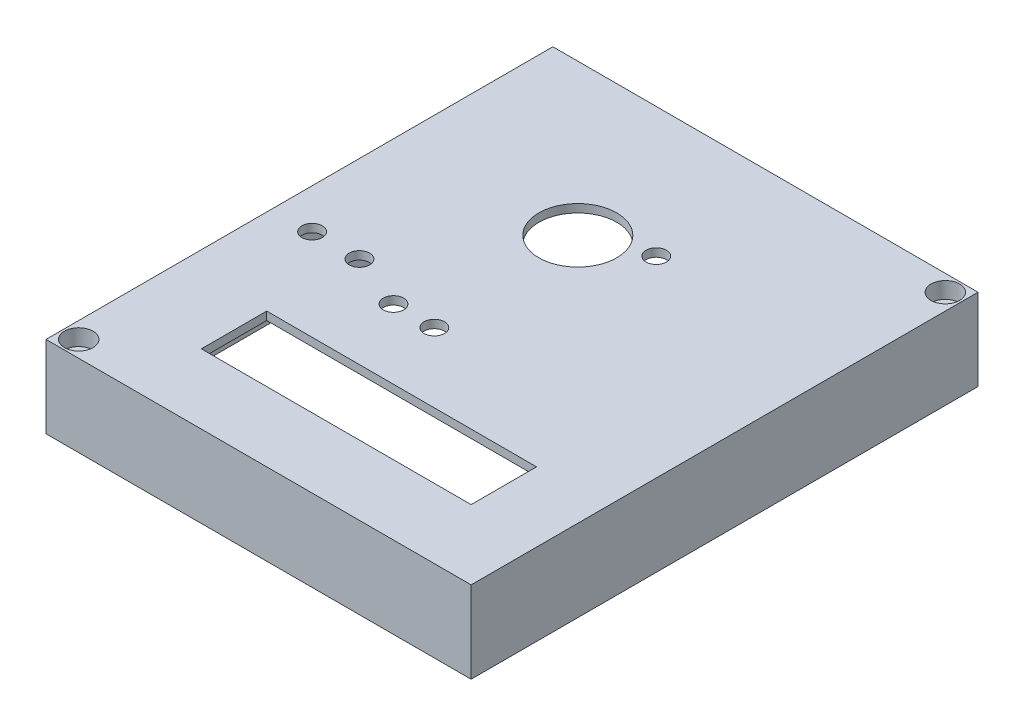
SolidWorks part; units mm, degrees
ref_plane "Front Plane" through (0, 0, 0) normal (0, 0, 1) x (1, 0, 0)
ref_plane "Top Plane" through (0, 0, 0) normal (0, 1, 0) x (1, 0, 0)
ref_plane "Right Plane" through (0, 0, 0) normal (1, 0, 0) x (0, 0, -1)
sketch "Sketch1" plane through (0, 0, 0) normal (0, 1, 0) x (1, 0, 0)
  line L1 (-52, -62) -> (52, -62)
  line L2 (-52, -62) -> (-52, 62)
  line L3 (-52, 62) -> (52, 62)
  line L4 (52, -62) -> (52, 62)
  line L5 (-52, -62) -> (52, 62) construction
  line L6 (-52, 62) -> (52, -62) construction
  point P0 (0, 0)
  dimension "D1" = 104
  dimension "D2" = 124
extrude "Boss-Extrude1" add sketch "Sketch1" along normal blind 2
sketch "Sketch4" plane through (0, 0, 0) normal (0, -1, 0) x (1, 0, 0)
  line L0 (-44, 58) -> (-44, 54)
  line L1 (-44, 54) -> (-48, 54)
  line L2 (44, -58) -> (44, -54)
  line L3 (44, -54) -> (48, -54)
  line L4 (52, -62) -> (52, 62)
  line L5 (52, 62) -> (-52, 62)
  line L6 (-52, 62) -> (-52, -62)
  line L7 (-52, -62) -> (52, -62)
  line L8 (52, -62) -> (52, 62)
  line L9 (52, 62) -> (-52, 62)
  line L10 (-52, 62) -> (-52, -62)
  line L11 (-52, -62) -> (52, -62)
  line L24 (48, -58) -> (48, 58)
  line L25 (48, 58) -> (-48, 58)
  line L26 (-48, 58) -> (-48, -58)
  line L27 (-48, -58) -> (48, -58)
  line L28 (48, -54) -> (48, 58)
  line L29 (48, 58) -> (-44, 58)
  line L30 (-48, 54) -> (-48, -58)
  line L31 (-48, -58) -> (44, -58)
  dimension "D4" = 4
  dimension "D6" = 4
  dimension "D1" = 0
  dimension "D2" = 4
extrude "Boss-Extrude2" add sketch "Sketch4" along normal blind 18
sketch "Sketch5" plane through (0, 2, 0) normal (0, 1, 0) x (1, 0, 0)
  line L0 (-52, -62) -> (52, -62) construction
  line L1 (-31, -45) -> (35, -45)
  line L2 (-31, -45) -> (-31, -29)
  line L3 (-31, -29) -> (35, -29)
  line L4 (35, -45) -> (35, -29)
  line L5 (-31, -45) -> (35, -29) construction
  line L6 (-31, -29) -> (35, -45) construction
  line L7 (52, 62) -> (-52, 62) construction
  line L8 (52, -62) -> (52, 62) construction
  line L10 (-52, 62) -> (-52, -62) construction
  circle A0 centre (-9, 25.1) radius 9.525
  circle A1 centre (-42.27, -6.63) radius 2.5
  circle A2 centre (-30.7, -6.63) radius 2.5
  circle A3 centre (-17, -12) radius 2.5
  circle A4 centre (-7, -12) radius 2.5
  circle A5 centre (5, 30.28) radius 2.5
  point P0 (2, -37)
  point P25 (0, 0)
  point P26 (0, 0)
  point P27 (0, 0)
  dimension "D4" = 19.05
  dimension "D8" = 5
  dimension "D9" = 5
  dimension "D1" = 66
  dimension "D2" = 16
  dimension "D3" = 17
  dimension "D5" = 36.9
  dimension "D6" = 43
  dimension "D7" = 21
  dimension "D10" = 9.73
  dimension "D11" = 21.3
  dimension "D12" = 47
  dimension "D13" = 31.72
  dimension "D14" = 35
  dimension "D15" = 45
  dimension "D16" = 55.37
  dimension "D17" = 50
extrude "Cut-Extrude1" cut sketch "Sketch5" against normal up to next
sketch "Sketch6" plane through (0, 2, 0) normal (0, 1, 0) x (1, 0, 0)
  line L0 (52, 62) -> (-52, 62) construction
  line L1 (52, -62) -> (52, 62) construction
  line L2 (-52, -62) -> (52, -62) construction
  line L3 (-52, 62) -> (-52, -62) construction
  circle A0 centre (48, 58) radius 2
  circle A1 centre (-48, -58) radius 2
  dimension "D1" = 4
  dimension "D4" = 4
  dimension "D2" = 4
  dimension "D3" = 4
  dimension "D5" = 4
  dimension "D6" = 4
extrude "Cut-Extrude2" cut sketch "Sketch6" against normal through all
sketch "Sketch7" plane through (0, 2, 0) normal (0, 1, 0) x (1, 0, 0)
  circle A0 centre (-48, -58) radius 3.5
  circle A1 centre (48, 58) radius 3.5
  dimension "D1" = 7
  dimension "D2" = 7
extrude "Cut-Extrude3" cut sketch "Sketch7" against normal blind 4
